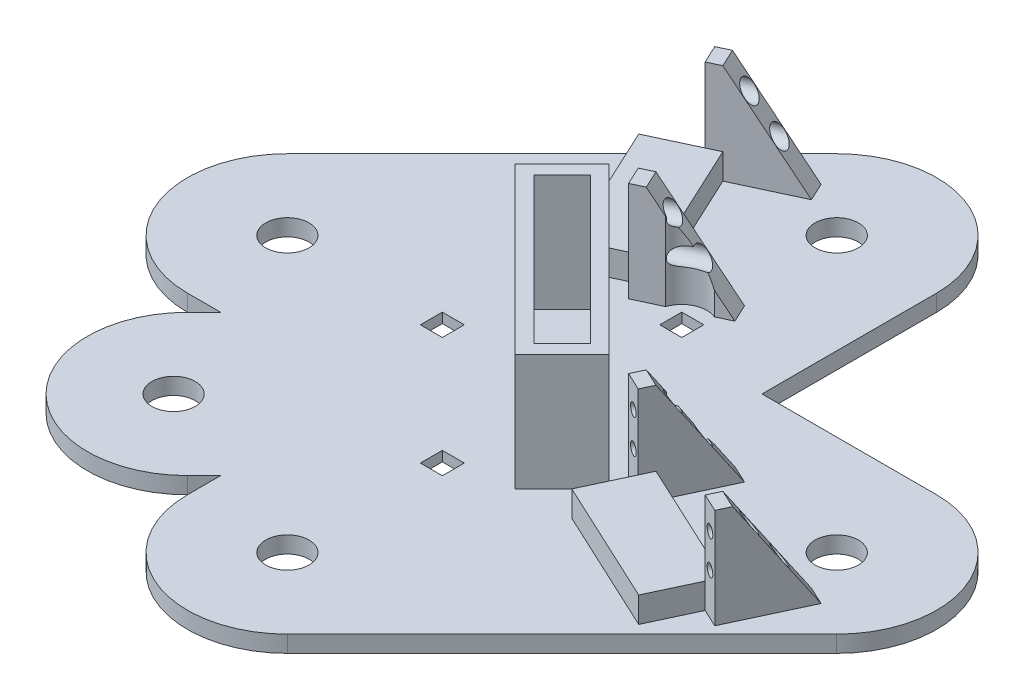
SolidWorks part; units mm, degrees
ref_plane "Front" through (0, 0, 0) normal (0, 0, 1) x (1, 0, 0)
ref_plane "Top" through (0, 0, 0) normal (0, 1, 0) x (1, 0, 0)
ref_plane "Right" through (0, 0, 0) normal (1, 0, 0) x (0, 0, -1)
sketch "Esquisse1" plane through (0, 0, 0) normal (0, 1, 0) x (1, 0, 0)
  line L0 (0, -2.4264) -> (0, -82.4264) construction
  line L1 (30, -2.4264) -> (30, -82.4264)
  line L2 (-30, -2.4264) -> (-30, -82.4264)
  line L3 (-2.4264, 0) -> (-82.4264, 0) construction
  line L4 (-2.4264, -30) -> (-82.4264, -30)
  line L5 (-2.4264, 30) -> (-82.4264, 30)
  line L6 (0, 2.4264) -> (0, 82.4264) construction
  line L7 (-30, 2.4264) -> (-30, 82.4264)
  line L8 (30, 2.4264) -> (30, 82.4264)
  line L9 (2.4264, 0) -> (82.4264, 0) construction
  line L10 (2.4264, 30) -> (82.4264, 30)
  line L11 (2.4264, -30) -> (82.4264, -30)
  line L12 (-82.4264, -30) -> (-30, -82.4264) construction
  line L15 (0, 42.4264) -> (42.4264, 0) construction
  line L16 (42.4264, 0) -> (0, -42.4264) construction
  line L17 (0, -42.4264) -> (-42.4264, 0) construction
  line L18 (-42.4264, 0) -> (0, 42.4264) construction
  line L19 (-42.4264, 0) -> (42.4264, 0) construction
  line L20 (0, -42.4264) -> (0, 42.4264) construction
  line L21 (0, 0) -> (-56.2132, -56.2132) construction
  line L22 (21.2132, -21.2132) -> (-35, -77.4264)
  line L23 (-21.2132, 21.2132) -> (-77.4264, -35)
  line L24 (-103.6396, 21.2132) -> (-21.2132, 103.6396)
  line L25 (21.2132, -103.6396) -> (103.6396, -21.2132)
  arc A0 (30, -2.4264) -> (-30, -2.4264) centre (0, -2.4264) ccw
  arc A1 (-30, -82.4264) -> (30, -82.4264) centre (0, -82.4264) ccw
  arc A2 (-2.4264, -30) -> (-2.4264, 30) centre (-2.4264, 0) ccw
  arc A3 (-82.4264, 30) -> (-82.4264, -30) centre (-82.4264, 0) ccw
  arc A4 (-30, 2.4264) -> (30, 2.4264) centre (0, 2.4264) ccw
  arc A5 (30, 82.4264) -> (-30, 82.4264) centre (0, 82.4264) ccw
  arc A6 (2.4264, 30) -> (2.4264, -30) centre (2.4264, 0) ccw
  arc A7 (82.4264, -30) -> (82.4264, 30) centre (82.4264, 0) ccw
  arc A10 (21.2132, -21.2132) -> (-21.2132, 21.2132) centre (0, 0) ccw
  arc A11 (-77.4264, -35) -> (-35, -77.4264) centre (-56.2132, -56.2132) ccw
  point P3 (0, -42.4264)
  point P10 (-42.4264, 0)
  point P17 (0, 42.4264)
  point P24 (42.4264, 0)
  point P33 (-28.1066, -28.1066)
  point P38 (0, 0)
  dimension "D2" = 30
  dimension "D3" = 30
  dimension "D6" = 30
  dimension "D8" = 30
  dimension "D9" = 30
  dimension "D1" = 80
  dimension "D4" = 80
  dimension "D5" = 80
  dimension "D7" = 80
  dimension "D10" = 79.4975
  dimension "D11" = 60
  dimension "D12" = 60
  dimension "D13" = 60
extrude "Boss.-Extru.1" add sketch "Esquisse1" along normal blind 5 contours L23 A11 L22 L2 L4 | L5 A3 L4 L23 L7 | A5 L24 A3 L5 L7 | A10 A6 L10 L8 A5 L7 L5 A2 | A10 A2 L5 L7 L23 | A2 A10 L23 L7 A4 A0 A6 | A4 L7 L23 L4 L2 A0 | A6 A4 A0 L2 L4 A2 | A6 A2 L4 L2 L22 L11 | L22 A10 A0 A4 A2 A6 L11 | A10 L22 L11 L1 A0 | A10 A4 L8 L10 A6 | A2 A6 A0 | A6 A0 A4 | A4 A6 A2 | A1 L1 L11 L22 L2 | A10 A0 L1 L11 A7 L10 L8 A4 | A7 L11 L1 A1 L25 | A0 A6 A4 A2 | A2 A4 A0 | A4 A10 A6 A2 A0 | A6 A10 A2 | A0 A10 A4 region at (68.2889, 0, 0) region at (24.5931, 0, 22.7559) region at (51.79, 0, 51.79) region at (3.9002, 0, 74.2281) region at (27.0901, 0, 11.8685) region at (29.9632, 0, 0) region at (-15.8551, 0, 44.1396) region at (26.4892, 0, 10.7569) region at (27.2371, 0, -11.1291) region at (23.3005, 0, -23.3005) region at (-56.5066, 0, 56.5066) region at (0, 0, 0) region at (0, 0, -27.9851) region at (10.7569, 0, 26.4892) region at (0, 0, -68.2889) region at (0, 0, -29.9632) region at (-22.5951, 0, 22.5951) region at (-44.1396, 0, 15.8551) region at (-27.9851, 0, 0) region at (-27.2373, 0, -11.1292) region at (-22.7559, 0, -24.5931) region at (-74.2281, 0, -3.9002) region at (-51.79, 0, -51.79)
sketch "Esquisse2" plane through (0, 0, 0) normal (0, -1, 0) x (1, 0, 0)
  circle A0 centre (82.4264, 0) radius 6.5
  circle A1 centre (58.2843, -58.2843) radius 6.5 [skipped]
  circle A2 centre (0, -82.4264) radius 6.5
  circle A3 centre (-58.2843, -58.2843) radius 6.5 [skipped]
  circle A4 centre (-82.4264, 0) radius 6.5
  circle A5 centre (-58.2843, 58.2843) radius 6.5
  circle A6 centre (0, 82.4264) radius 6.5
  circle A7 centre (58.2843, 58.2843) radius 6.5 [skipped]
  point P20 (0, 0)
  dimension "D1" = 13
  dimension "D2" = 8
extrude "Enlèv. mat.-Extru.1" cut sketch "Esquisse2" against normal through all
sketch "Esquisse3" plane through (0, 0, 0) normal (0, -1, 0) x (1, 0, 0)
  line L0 (0, 0) -> (82.4264, 0) construction
  line L1 (50.8036, 15) -> (25.8036, 15)
  line L2 (25.8036, 15) -> (25.8036, -15)
  line L3 (25.8036, -15) -> (50.8036, -15)
  line L4 (-15, -25.8036) -> (-15, -50.8036)
  line L5 (15, -50.8036) -> (15, -25.8036)
  line L6 (15, -25.8036) -> (-15, -25.8036)
  line L7 (-25.8036, 15) -> (-50.8036, 15)
  line L8 (-50.8036, -15) -> (-25.8036, -15)
  line L9 (-25.8036, -15) -> (-25.8036, 15)
  line L10 (15, 25.8036) -> (15, 50.8036)
  line L11 (-15, 50.8036) -> (-15, 25.8036)
  line L12 (-15, 25.8036) -> (15, 25.8036)
  arc A0 (50.8036, -15) -> (50.8036, 15) centre (82.4264, 0) cw
  arc A1 (-15, -50.8036) -> (15, -50.8036) centre (0, -82.4264) cw
  arc A2 (-50.8036, 15) -> (-50.8036, -15) centre (-82.4264, 0) cw
  arc A3 (15, 50.8036) -> (-15, 50.8036) centre (0, 82.4264) cw
  point P26 (0, 0)
  dimension "D4" = 35
  dimension "D1" = 30
  dimension "D2" = 25
  dimension "D3" = 25
  dimension "D5" = 4
extrude "Enlèv. mat.-Extru.2" cut sketch "Esquisse3" against normal blind 2
sketch "Esquisse4" plane through (0, 5, 0) normal (0, 1, 0) x (1, 0, 0)
  line L0 (0, 0) -> (82.4264, 0) construction
  circle A0 centre (35.9264, 0) radius 3.25
  dimension "D1" = 6.5
  dimension "D2" = 46.5
extrude "Enlèv. mat.-Extru.3" cut sketch "Esquisse4" against normal through all
sketch "Esquisse5" plane through (0, 5, 0) normal (0, 1, 0) x (1, 0, 0)
  line L1 (32.6264, -3.3) -> (39.2264, -3.3)
  line L2 (32.6264, -3.3) -> (32.6264, 3.3)
  line L3 (32.6264, 3.3) -> (39.2264, 3.3)
  line L4 (39.2264, -3.3) -> (39.2264, 3.3)
  line L5 (32.6264, -3.3) -> (39.2264, 3.3) construction
  line L6 (32.6264, 3.3) -> (39.2264, -3.3) construction
  point P0 (35.9264, 0)
  dimension "D1" = 6.6
  dimension "D2" = 6.6
extrude "Enlèv. mat.-Extru.4" cut sketch "Esquisse5" against normal through all
ref_axis "Axe1" through (0, 50, 0) along (0, -1, 0)
pattern_circular "Répétition circulaire1" count 4 over 360 about axis through (0, 50, 0) along (0, -1, 0) of "Enlèv. mat.-Extru.4"
sketch "Esquisse6" plane through (0, 5, 0) normal (0, 1, 0) x (1, 0, 0)
  line L0 (31.8198, -17.6777) -> (-17.6777, 31.8198)
  line L1 (-17.6777, 31.8198) -> (-31.8198, 17.6777)
  line L2 (-31.8198, 17.6777) -> (17.6777, -31.8198)
  line L3 (17.6777, -31.8198) -> (31.8198, -17.6777)
  line L4 (17.6777, -31.8198) -> (-17.6777, 31.8198) construction
  line L5 (-31.8198, 17.6777) -> (31.8198, -17.6777) construction
  line L6 (17.6777, -26.163) -> (26.163, -17.6777)
  line L11 (26.163, -17.6777) -> (-17.6777, 26.163)
  line L12 (-17.6777, 26.163) -> (-26.163, 17.6777)
  line L13 (-26.163, 17.6777) -> (17.6777, -26.163)
  line L14 (17.6777, -26.163) -> (-17.6777, 26.163) construction
  line L15 (-26.163, 17.6777) -> (26.163, -17.6777) construction
  point P4 (0, 0)
  point P10 (0, 0)
  dimension "D1" = 20
  dimension "D2" = 70
  dimension "D3" = 12
  dimension "D4" = 62
extrude "Boss.-Extru.2" add sketch "Esquisse6" along normal blind 35
sketch "Esquisse7" plane through (7.0711, 0, -7.0711) normal (0.7071, 0, -0.7071) x (-0.7071, 0, -0.7071)
  line L0 (-35, 40) -> (35, 40) construction
  line L1 (-35, 40) -> (-35, 5) construction
  circle A0 centre (0, 34) radius 3.25
  dimension "D1" = 6.5
  dimension "D2" = 6
  dimension "D3" = 35
extrude "Enlèv. mat.-Extru.5" cut sketch "Esquisse7" against normal through all
sketch "Esquisse8" plane through (7.0711, 0, -7.0711) normal (0.7071, 0, -0.7071) x (-0.7071, 0, -0.7071)
  line L1 (-3.3, 37.3) -> (3.3, 37.3)
  line L2 (-3.3, 37.3) -> (-3.3, 30.7)
  line L3 (-3.3, 30.7) -> (3.3, 30.7)
  line L4 (3.3, 37.3) -> (3.3, 30.7)
  line L5 (-3.3, 37.3) -> (3.3, 30.7) construction
  line L6 (-3.3, 30.7) -> (3.3, 37.3) construction
  point P0 (0, 34)
  dimension "D1" = 6.6
  dimension "D2" = 6.6
extrude "Enlèv. mat.-Extru.6" cut sketch "Esquisse8" against normal up to next
sketch "Esquisse9" plane through (7.0711, 0, -7.0711) normal (0.7071, 0, -0.7071) x (-0.7071, 0, -0.7071)
  line L0 (-10, 10) -> (10, 10)
  line L1 (10, 10) -> (0, 20)
  line L2 (0, 20) -> (-10, 10)
  line L3 (-35, 5) -> (35, 5) construction
  line L4 (-35, 40) -> (-35, 5) construction
  dimension "D1" = 20
  dimension "D2" = 45
  dimension "D3" = 5
  dimension "D4" = 35
extrude "Enlèv. mat.-Extru.7" cut sketch "Esquisse9" against normal through all
sketch "Esquisse10" plane through (0, 5, 0) normal (0, 1, 0) x (1, 0, 0)
  line L0 (82.4264, 0) -> (67.9746, 14.4518) construction
  line L1 (82.4264, 0) -> (57.3066, -53.8697) construction
  line L2 (31.8198, -17.6777) -> (-17.6777, 31.8198) construction
  line L3 (87.6695, -39.4341) -> (33.291, -14.077) construction
  line L4 (83.1784, -37.3398) -> (77.7405, -34.8041)
  line L5 (77.7405, -34.8041) -> (79.431, -31.1789)
  line L6 (79.431, -31.1789) -> (84.8688, -33.7146)
  line L7 (84.8688, -33.7146) -> (83.1784, -37.3398)
  line L8 (34.6909, -14.7298) -> (40.1287, -17.2655)
  line L9 (40.1287, -17.2655) -> (41.8192, -13.6402)
  line L10 (41.8192, -13.6402) -> (36.3814, -11.1045)
  line L11 (36.3814, -11.1045) -> (34.6909, -14.7298)
  point P14 (80.4594, -36.072)
  point P17 (37.4098, -15.9976)
  dimension "D1" = 110
  dimension "D2" = 33.5236
  dimension "D3" = 60
  dimension "D4" = 6
  dimension "D5" = 4
  dimension "D6" = 6
  dimension "D7" = 4
  dimension "D8" = 47.5
  dimension "D9" = 13.462
extrude "Boss.-Extru.3" add sketch "Esquisse10" along normal blind 30
sketch "Esquisse11" plane through (0, 5, 0) normal (0, 1, 0) x (1, 0, 0)
  line L0 (79.431, -31.1789) -> (41.8192, -13.6402)
  line L1 (41.8192, -13.6402) -> (33.7895, -30.8601)
  line L2 (33.7895, -30.8601) -> (71.4012, -48.3987)
  line L3 (71.4012, -48.3987) -> (79.431, -31.1789)
  line L4 (77.7405, -34.8041) -> (83.1784, -37.3398) construction
  point P8 (80.4594, -36.072)
  dimension "D1" = 15
extrude "Boss.-Extru.4" add sketch "Esquisse11" along normal blind 7.644
sketch "Esquisse12" plane through (0, 5, 0) normal (0, 1, 0) x (1, 0, 0)
  line L0 (84.8688, -33.7146) -> (93.3212, -15.5885)
  line L1 (93.3212, -15.5885) -> (87.8834, -13.0527)
  line L2 (87.8834, -13.0527) -> (79.431, -31.1789)
  line L3 (84.8688, -33.7146) -> (36.3814, -11.1045) construction
  line L4 (79.431, -31.1789) -> (84.8688, -33.7146)
  line L5 (36.3814, -11.1045) -> (41.8192, -13.6402)
  line L6 (41.8192, -13.6402) -> (50.2716, 4.4859)
  line L7 (50.2716, 4.4859) -> (44.8337, 7.0216)
  line L8 (44.8337, 7.0216) -> (36.3814, -11.1045)
  dimension "D1" = 20
  dimension "D2" = 6
  dimension "D3" = 6
  dimension "D4" = 20
extrude "Boss.-Extru.5" add sketch "Esquisse12" along normal blind 30
sketch "Esquisse13" plane through (82.6242, 0, 38.5283) normal (0.9063, 0, 0.4226) x (0.4226, 0, -0.9063)
  line L0 (25.3113, 5) -> (25.3113, 35)
  line L1 (25.3113, 35) -> (5.3113, 35)
  line L2 (1.3113, 35) -> (25.3113, 35) construction
  line L3 (5.3113, 35) -> (25.3113, 5)
  dimension "D1" = 4
extrude "Enlèv. mat.-Extru.8" cut sketch "Esquisse13" against normal up to surface (53.5 mm away) up to face at (39.7623, 20, 3.8541)
ref_plane "Plan1" through (2.2447, 0, -4.8137) normal (-0.4226, 0, 0.9063) x (0.9063, 0, 0.4226)
sketch "Esquisse14" plane through (2.2447, 0, -4.8137) normal (-0.4226, 0, 0.9063) x (0.9063, 0, 0.4226)
  line L0 (85.1657, 5) -> (43.6657, 5) construction
  line L1 (43.6657, 5) -> (43.6657, 35) construction
  circle A0 centre (40.6657, 27.63) radius 1.75
  circle A1 centre (40.6657, 17.47) radius 1.75
  dimension "D1" = 3.5
  dimension "D2" = 3.5
  dimension "D3" = 12.47
  dimension "D4" = 22.63
  dimension "D5" = 3
  dimension "D6" = 3
extrude "Enlèv. mat.-Extru.9" cut sketch "Esquisse14" against normal through all both and the other way through all
sketch "Esquisse15" plane through (2.2447, 0, -4.8137) normal (-0.4226, 0, 0.9063) x (0.9063, 0, 0.4226)
  circle A0 centre (40.6657, 27.63) radius 2.9
  circle A1 centre (40.6657, 17.47) radius 2.9
  dimension "D1" = 5.8
  dimension "D2" = 5.8
extrude "Enlèv. mat.-Extru.10" cut sketch "Esquisse15" against normal through all
ref_plane "Plan2" through (58.3804, 0, 27.2232) normal (0.9063, 0, 0.4226) x (0.4226, 0, -0.9063)
mirror "Symétrie1" about plane through (58.3804, 0, 27.2232) normal (0.9063, 0, 0.4226) of "Enlèv. mat.-Extru.10", "Enlèv. mat.-Extru.9"
sketch "Esquisse16" plane through (0, 5, 0) normal (0, 1, 0) x (1, 0, 0)
  line L0 (32.6264, 3.3) -> (32.6264, -3.3) construction
  line L1 (32.6264, -3.3) -> (39.2264, -3.3) construction
  circle A0 centre (35.9264, 0) radius 7.5
  dimension "D1" = 15
  dimension "D2" = 3.3
  dimension "D3" = 3.3
extrude "Enlèv. mat.-Extru.12" cut sketch "Esquisse16" along normal blind 30
ref_plane "Plan3" through (0, 0, 0) normal (0.7071, 0, 0.7071) x (0.7071, 0, -0.7071)
mirror "Symétrie2" about plane through (0, 0, 0) normal (0.7071, 0, 0.7071) of "Enlèv. mat.-Extru.12", "Boss.-Extru.3", "Boss.-Extru.5", "Boss.-Extru.4", "Enlèv. mat.-Extru.8", "Enlèv. mat.-Extru.9", "Enlèv. mat.-Extru.10", "Symétrie1"
